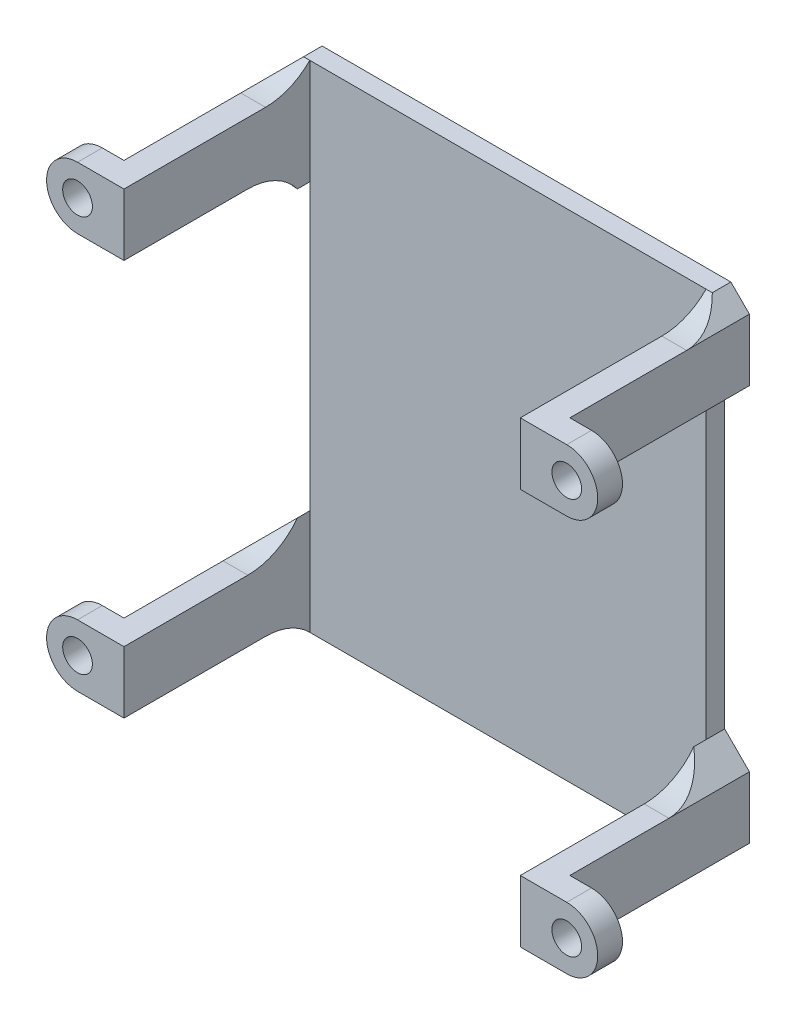
SolidWorks part; units mm, degrees
ref_plane "Front Plane" through (0, 0, 0) normal (0, 0, 1) x (1, 0, 0)
ref_plane "Top Plane" through (0, 0, 0) normal (0, 1, 0) x (1, 0, 0)
ref_plane "Right Plane" through (0, 0, 0) normal (1, 0, 0) x (0, 0, -1)
sketch "Sketch1" plane through (0, 0, 0) normal (0, 0, 1) x (1, 0, 0)
  line L0 (0, 26.8005) -> (0, -28.5872) construction
  line L1 (-32.9736, 0) -> (26.0867, 0) construction
  line L2 (16, 20) -> (-16, 20)
  line L3 (-16, 20) -> (-16, -20)
  line L4 (16, -20) -> (-16, -20)
  line L5 (16, 20) -> (16, -20)
  point P9 (-16, 0)
  point P10 (16, 0)
  point P12 (0, -20)
  point P13 (0, 20)
  dimension "D1" = 32
  dimension "D2" = 40
extrude "Boss-Extrude1" add sketch "Sketch1" along normal blind 1.5
sketch "Sketch2" plane through (0, 0, 0) normal (0, 0, 1) x (1, 0, 0)
  line L0 (0, 39.3321) -> (0, -30.6577) construction
  line L1 (-36.8367, 0) -> (38.1438, 0) construction
  line L2 (-30.7253, 16) -> (28.37, 16) construction
  line L3 (-16, 18.5) -> (-19.75, 18.5)
  line L4 (-16, 20) -> (-16, -20) construction
  line L5 (-16, 13.5) -> (-19.75, 13.5)
  line L6 (-16, 18.5) -> (-16, 13.5)
  line L7 (16, 18.5) -> (16, 13.5)
  line L8 (16, 13.5) -> (19.75, 13.5)
  line L9 (16, 18.5) -> (19.75, 18.5)
  line L10 (16, -18.5) -> (19.75, -18.5)
  line L11 (16, -13.5) -> (19.75, -13.5)
  line L12 (16, -18.5) -> (16, -13.5)
  line L13 (-16, -18.5) -> (-16, -13.5)
  line L14 (-16, -13.5) -> (-19.75, -13.5)
  line L15 (-16, -18.5) -> (-19.75, -18.5)
  circle A0 centre (-19.75, 16) radius 1.2
  arc A1 (-19.75, 18.5) -> (-19.75, 13.5) centre (-19.75, 16) ccw
  arc A2 (19.75, 18.5) -> (19.75, 13.5) centre (19.75, 16) cw
  circle A3 centre (19.75, 16) radius 1.2
  circle A4 centre (19.75, -16) radius 1.2
  arc A5 (19.75, -18.5) -> (19.75, -13.5) centre (19.75, -16) ccw
  arc A6 (-19.75, -18.5) -> (-19.75, -13.5) centre (-19.75, -16) cw
  circle A7 centre (-19.75, -16) radius 1.2
  dimension "D3" = 2.4
  dimension "D4" = 2.5
  dimension "D1" = 16
  dimension "D2" = 19.75
extrude "Boss-Extrude2" add sketch "Sketch2" along normal blind 16.5
sketch "Sketch4" plane through (0, 0, 0) normal (0, 1, 0) x (1, 0, 0)
  line L0 (0, 10.6908) -> (0, -22.3136) construction
  line L1 (-18, 0) -> (-18, -14.5)
  line L2 (-16, 0) -> (-19.75, 0) construction
  line L3 (-18, -14.5) -> (-28, -14.5)
  line L4 (-28, -14.5) -> (-28, 0)
  line L5 (-28, 0) -> (-18, 0)
  line L6 (-16, -16.5) -> (-16, -1.5) construction
  line L7 (-16, -16.5) -> (-19.75, -16.5) construction
  line L8 (28, 0) -> (18, 0)
  line L9 (28, -14.5) -> (28, 0)
  line L10 (18, -14.5) -> (28, -14.5)
  line L11 (18, 0) -> (18, -14.5)
  dimension "D1" = 2
  dimension "D2" = 2
  dimension "D3" = 10
extrude "Cut-Extrude1" cut sketch "Sketch4" against normal through all both and the other way through all
chamfer "Chamfer1" distance 2 angle 45 8 edges at (-16, -13.5, 0.75) (-16, -18.5, 0.75) (-16, 13.5, 0.75) (-16, 18.5, 0.75) (16, -18.5, 0.75) (16, -13.5, 0.75) (16, 13.5, 0.75) (16, 18.5, 0.75)
fillet "Fillet1" radius 5 6 edges at (17, -18.5, 1.5) (17, -13.5, 1.5) (17, 18.5, 1.5) (-17, 18.5, 1.5) (-17, 13.5, 1.5) (-17, -18.5, 1.5)
